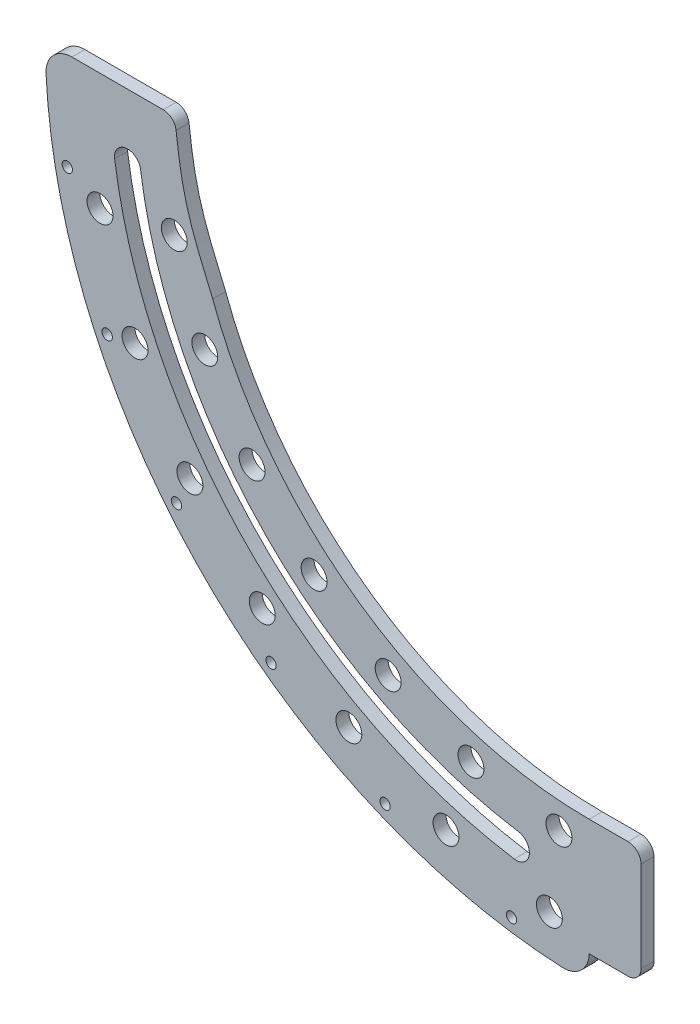
SolidWorks part; units mm, degrees
ref_plane "Front Plane" through (0, 0, 0) normal (0, 0, 1) x (1, 0, 0)
ref_plane "Top Plane" through (0, 0, 0) normal (0, 1, 0) x (1, 0, 0)
ref_plane "Right Plane" through (0, 0, 0) normal (1, 0, 0) x (0, 0, -1)
sketch "Layout" plane through (0, 0, 0) normal (0, 0, 1) x (1, 0, 0)
  line L0 (0, 0) -> (-76.2, 0) construction
  line L1 (-76.2, 0) -> (-203.2, 0) construction
  line L2 (-203.2, 0) -> (-254, 0) construction
  dimension "D1" = 76.2
  dimension "D2" = 127
  dimension "D3" = 50.8
sketch "Sketch1" plane through (0, 0, 0) normal (0, 0, 1) x (1, 0, 0)
  line L0 (0, 0) -> (-203.2, 0) construction
  line L1 (0, 0) -> (0, -203.2) construction
  line L2 (0, -203.2) -> (25.4, -203.2)
  line L3 (0, -254) -> (25.4, -254)
  line L4 (-254, 0) -> (-203.2, 0)
  line L5 (25.4, -203.2) -> (25.4, -254)
  arc A0 (-203.2, 0) -> (0, -203.2) centre (0, 0) ccw
  arc A1 (-254, 0) -> (0, -254) centre (0, 0) ccw
  dimension "D1" = 50.8
  dimension "D2" = 25.4
  dimension "D3" = 203.2
extrude "Boss-Extrude1" add sketch "Sketch1" along normal blind 6.35
ref_plane "Mid_Plane" through (0, 0, 3.175) normal (0, 0, 1) x (1, 0, 0)
sketch "Sketch2" plane through (0, 0, 6.35) normal (0, 0, 1) x (1, 0, 0)
  line L0 (0, 0) -> (-229.3095, 0) construction
  line L1 (0, 0) -> (-226.3753, -31.815) construction
  line L2 (0, 0) -> (-35.7609, -225.7856) construction
  arc A0 (-226.3753, -31.815) -> (-35.7609, -225.7856) centre (0, 0) ccw construction
  arc A1 (-226.3753, -31.815) -> (-35.7609, -225.7856) centre (0, 0) ccw construction
  arc A2 (-232.7264, -32.7076) -> (-36.7642, -232.1201) centre (0, 0) ccw
  arc A3 (-220.0242, -30.9224) -> (-34.7576, -219.451) centre (0, 0) ccw
  arc A4 (-220.0242, -30.9224) -> (-232.7264, -32.7076) centre (-226.3753, -31.815) ccw
  arc A5 (-36.7642, -232.1201) -> (-34.7576, -219.451) centre (-35.7609, -225.7856) ccw
  point P5 (-163.0491, -160.2279)
  dimension "D1" = 73
  dimension "D3" = 12.827
  dimension "D4" = 228.6
  dimension "D2" = 8
extrude "Cut-Extrude1" cut sketch "Sketch2" against normal up to next
fillet "Fillet1" [suppressed] radius 12.7
ref_point "Mid_Point"
sketch "Sketch4" plane through (0, 0, 0) normal (0, 0, -1) x (-1, 0, 0)
  line L0 (254, 0) -> (266.7, 0)
  line L1 (0, -254) -> (0, -266.7)
  arc A0 (0, -254) -> (254, 0) centre (0, 0) ccw construction
  arc A1 (0, -254) -> (254, 0) centre (0, 0) ccw
  arc A2 (0, -266.7) -> (266.7, 0) centre (0, 0) ccw
extrude "Boss-Extrude3" add sketch "Sketch4" against normal up to surface (6.35 mm away) up to face at (-145.6981, -143.1771, 6.35)
fillet "Fillet2" radius 12.7 2 edges at (-266.7, 0, 3.175) (0, -266.7, 3.175)
sketch "Sketch5" plane through (0, 0, 0) normal (0, 0, -1) x (-1, 0, 0)
  line L0 (2.758, -261.6055) -> (3.6103, -266.6756)
  line L1 (0, 0) -> (306.4939, -16.1536) construction
  line L2 (0, -261.62) -> (0.7987, -266.6988)
  line L3 (0, -261.62) -> (-1.3603, -266.6965)
  line L4 (2.758, -261.6055) -> (1.4514, -266.6961)
  line L5 (5.5157, -261.5618) -> (6.4214, -266.6227)
  line L6 (5.5157, -261.5618) -> (4.2628, -266.6659)
  line L7 (8.2728, -261.4892) -> (9.2318, -266.5402)
  line L8 (8.2728, -261.4892) -> (7.0738, -266.6062)
  line L9 (11.029, -261.3874) -> (12.0411, -266.428)
  line L10 (11.029, -261.3874) -> (9.884, -266.5168)
  line L11 (13.7839, -261.2566) -> (14.8492, -266.2863)
  line L12 (13.7839, -261.2566) -> (12.693, -266.3978)
  line L13 (16.5374, -261.0968) -> (17.6555, -266.115)
  line L14 (16.5374, -261.0968) -> (15.5007, -266.2492)
  line L15 (19.2889, -260.908) -> (20.46, -265.914)
  line L16 (19.2889, -260.908) -> (18.3067, -266.071)
  line L17 (22.0384, -260.6901) -> (23.2621, -265.6836)
  line L18 (22.0384, -260.6901) -> (21.1106, -265.8632)
  line L19 (24.7854, -260.4433) -> (26.0617, -265.4236)
  line L20 (24.7854, -260.4433) -> (23.9122, -265.6259)
  line L21 (27.5296, -260.1675) -> (28.8583, -265.1341)
  line L22 (27.5296, -260.1675) -> (26.7111, -265.359)
  line L23 (30.2708, -259.8629) -> (31.6518, -264.8151)
  line L24 (30.2708, -259.8629) -> (29.507, -265.0627)
  line L25 (33.0086, -259.5293) -> (34.4417, -264.4667)
  line L26 (33.0086, -259.5293) -> (32.2997, -264.7369)
  line L27 (35.7427, -259.1669) -> (37.2278, -264.089)
  line L28 (35.7427, -259.1669) -> (35.0888, -264.3817)
  line L29 (38.4729, -258.7757) -> (40.0098, -263.6818)
  line L30 (38.4729, -258.7757) -> (37.874, -263.9971)
  line L31 (41.1988, -258.3557) -> (42.7873, -263.2454)
  line L32 (41.1988, -258.3557) -> (40.6549, -263.5831)
  line L33 (43.9201, -257.9071) -> (45.5601, -262.7797)
  line L34 (43.9201, -257.9071) -> (43.4314, -263.1399)
  line L35 (46.6365, -257.4297) -> (48.3278, -262.2848)
  line L36 (46.6365, -257.4297) -> (46.203, -262.6674)
  line L37 (49.3478, -256.9238) -> (51.0902, -261.7607)
  line L38 (49.3478, -256.9238) -> (48.9695, -262.1657)
  line L39 (52.0535, -256.3893) -> (53.8468, -261.2076)
  line L40 (52.0535, -256.3893) -> (51.7305, -261.6349)
  line L41 (54.7535, -255.8263) -> (56.5975, -260.6254)
  line L42 (54.7535, -255.8263) -> (54.4858, -261.0751)
  line L43 (57.4474, -255.2348) -> (59.3419, -260.0143)
  line L44 (57.4474, -255.2348) -> (57.2351, -260.4862)
  line L45 (60.1349, -254.615) -> (62.0797, -259.3743)
  line L46 (60.1349, -254.615) -> (59.978, -259.8683)
  line L47 (62.8157, -253.9669) -> (64.8106, -258.7054)
  line L48 (62.8157, -253.9669) -> (62.7142, -259.2216)
  line L49 (65.4896, -253.2906) -> (67.5342, -258.0078)
  line L50 (65.4896, -253.2906) -> (65.4434, -258.546)
  line L51 (68.1561, -252.5862) -> (70.2504, -257.2815)
  line L52 (68.1561, -252.5862) -> (68.1654, -257.8418)
  line L53 (70.8151, -251.8536) -> (72.9588, -256.5266)
  line L54 (70.8151, -251.8536) -> (70.8798, -257.1088)
  line L55 (73.4663, -251.0931) -> (75.6591, -255.7432)
  line L56 (73.4663, -251.0931) -> (73.5863, -256.3473)
  line L57 (76.1092, -250.3046) -> (78.3509, -254.9314)
  line L58 (76.1092, -250.3046) -> (76.2846, -255.5573)
  line L59 (78.7437, -249.4884) -> (81.0341, -254.0913)
  line L60 (78.7437, -249.4884) -> (78.9745, -254.7389)
  line L61 (81.3695, -248.6444) -> (83.7082, -253.2229)
  line L62 (81.3695, -248.6444) -> (81.6556, -253.8922)
  line L63 (83.9862, -247.7728) -> (86.373, -252.3263)
  line L64 (83.9862, -247.7728) -> (84.3276, -253.0173)
  line L65 (86.5935, -246.8736) -> (89.0283, -251.4018)
  line L66 (86.5935, -246.8736) -> (86.9902, -252.1142)
  line L67 (89.1913, -245.947) -> (91.6736, -250.4493)
  line L68 (89.1913, -245.947) -> (89.6432, -251.1832)
  line L69 (91.7791, -244.9931) -> (94.3088, -249.4689)
  line L70 (91.7791, -244.9931) -> (92.2862, -250.2242)
  line L71 (94.3567, -244.0119) -> (96.9335, -248.4608)
  line L72 (94.3567, -244.0119) -> (94.919, -249.2374)
  line L73 (96.9239, -243.0037) -> (99.5474, -247.4252)
  line L74 (96.9239, -243.0037) -> (97.5412, -248.2229)
  line L75 (99.4803, -241.9684) -> (102.1502, -246.362)
  line L76 (99.4803, -241.9684) -> (100.1525, -247.1808)
  line L77 (102.0256, -240.9062) -> (104.7417, -245.2714)
  line L78 (102.0256, -240.9062) -> (102.7528, -246.1113)
  line L79 (104.5596, -239.8173) -> (107.3215, -244.1536)
  line L80 (104.5596, -239.8173) -> (105.3416, -245.0144)
  line L81 (107.0819, -238.7017) -> (109.8895, -243.0086)
  line L82 (107.0819, -238.7017) -> (107.9187, -243.8902)
  line L83 (109.5924, -237.5595) -> (112.4452, -241.8367)
  line L84 (109.5924, -237.5595) -> (110.4838, -242.739)
  line L85 (112.0907, -236.391) -> (114.9884, -240.6378)
  line L86 (112.0907, -236.391) -> (113.0366, -241.5608)
  line L87 (114.5765, -235.1962) -> (117.5188, -239.4122)
  line L88 (114.5765, -235.1962) -> (115.5769, -240.3557)
  line L89 (117.0496, -233.9753) -> (120.0362, -238.16)
  line L90 (117.0496, -233.9753) -> (118.1043, -239.124)
  line L91 (119.5096, -232.7283) -> (122.5402, -236.8814)
  line L92 (119.5096, -232.7283) -> (120.6186, -237.8656)
  line L93 (121.9564, -231.4555) -> (125.0306, -235.5764)
  line L94 (121.9564, -231.4555) -> (123.1195, -236.5808)
  line L95 (124.3897, -230.157) -> (127.5071, -234.2452)
  line L96 (124.3897, -230.157) -> (125.6067, -235.2697)
  line L97 (126.8091, -228.8329) -> (129.9695, -232.888)
  line L98 (126.8091, -228.8329) -> (128.0799, -233.9325)
  line L99 (129.2144, -227.4833) -> (132.4174, -231.5049)
  line L100 (129.2144, -227.4833) -> (130.539, -232.5693)
  line L101 (131.6054, -226.1085) -> (134.8505, -230.0961)
  line L102 (131.6054, -226.1085) -> (132.9835, -231.1802)
  line L103 (133.9817, -224.7085) -> (137.2687, -228.6617)
  line L104 (133.9817, -224.7085) -> (135.4132, -229.7654)
  line L105 (136.3432, -223.2836) -> (139.6717, -227.2019)
  line L106 (136.3432, -223.2836) -> (137.8279, -228.3251)
  line L107 (138.6895, -221.8339) -> (142.0591, -225.7169)
  line L108 (138.6895, -221.8339) -> (140.2272, -226.8595)
  line L109 (141.0203, -220.3595) -> (144.4307, -224.2067)
  line L110 (141.0203, -220.3595) -> (142.611, -225.3686)
  line L111 (143.3355, -218.8606) -> (146.7863, -222.6717)
  line L112 (143.3355, -218.8606) -> (144.9789, -223.8526)
  line L113 (145.6348, -217.3374) -> (149.1256, -221.1119)
  line L114 (145.6348, -217.3374) -> (147.3307, -222.3118)
  line L115 (147.9179, -215.79) -> (151.4482, -219.5275)
  line L116 (147.9179, -215.79) -> (149.6662, -220.7463)
  line L117 (150.1846, -214.2186) -> (153.7541, -217.9187)
  line L118 (150.1846, -214.2186) -> (151.985, -219.1562)
  line L119 (152.4345, -212.6235) -> (156.0429, -216.2857)
  line L120 (152.4345, -212.6235) -> (154.2869, -217.5418)
  line L121 (154.6675, -211.0047) -> (158.3143, -214.6287)
  line L122 (154.6675, -211.0047) -> (156.5717, -215.9032)
  line L123 (156.8834, -209.3624) -> (160.5681, -212.9478)
  line L124 (156.8834, -209.3624) -> (158.839, -214.2407)
  line L125 (159.0818, -207.6969) -> (162.8041, -211.2432)
  line L126 (159.0818, -207.6969) -> (161.0887, -212.5543)
  line L127 (161.2625, -206.0083) -> (165.022, -209.5152)
  line L128 (161.2625, -206.0083) -> (163.3205, -210.8442)
  line L129 (163.4253, -204.2969) -> (167.2216, -207.7639)
  line L130 (163.4253, -204.2969) -> (165.5342, -209.1108)
  line L131 (165.5699, -202.5627) -> (169.4025, -205.9895)
  line L132 (165.5699, -202.5627) -> (167.7295, -207.3541)
  line L133 (167.6961, -200.806) -> (171.5647, -204.1922)
  line L134 (167.6961, -200.806) -> (169.9061, -205.5744)
  line L135 (169.8037, -199.0269) -> (173.7077, -202.3722)
  line L136 (169.8037, -199.0269) -> (172.0638, -203.7718)
  line L137 (171.8924, -197.2258) -> (175.8315, -200.5297)
  line L138 (171.8924, -197.2258) -> (174.2024, -201.9465)
  line L139 (173.962, -195.4027) -> (177.9357, -198.665)
  line L140 (173.962, -195.4027) -> (176.3217, -200.0989)
  line L141 (176.0123, -193.558) -> (180.0202, -196.7781)
  line L142 (176.0123, -193.558) -> (178.4213, -198.229)
  line L143 (178.043, -191.6917) -> (182.0846, -194.8694)
  line L144 (178.043, -191.6917) -> (180.5012, -196.337)
  line L145 (180.054, -189.8041) -> (184.1288, -192.939)
  line L146 (180.054, -189.8041) -> (182.5609, -194.4232)
  line L147 (182.0449, -187.8954) -> (186.1526, -190.9872)
  line L148 (182.0449, -187.8954) -> (184.6004, -192.4879)
  line L149 (184.0156, -185.9658) -> (188.1556, -189.0141)
  line L150 (184.0156, -185.9658) -> (186.6194, -190.5311)
  line L151 (185.9658, -184.0156) -> (190.1378, -187.0201)
  line L152 (185.9658, -184.0156) -> (188.6176, -188.5532)
  line L153 (187.8954, -182.0449) -> (192.0988, -185.0053)
  line L154 (187.8954, -182.0449) -> (190.5948, -186.5543)
  line L155 (189.8041, -180.054) -> (194.0384, -182.9699)
  line L156 (189.8041, -180.054) -> (192.5509, -184.5346)
  line L157 (191.6917, -178.043) -> (195.9565, -180.9141)
  line L158 (191.6917, -178.043) -> (194.4856, -182.4945)
  line L159 (193.558, -176.0123) -> (197.8529, -178.8383)
  line L160 (193.558, -176.0123) -> (196.3987, -180.4341)
  line L161 (195.4027, -173.962) -> (199.7272, -176.7426)
  line L162 (195.4027, -173.962) -> (198.2899, -178.3536)
  line L163 (197.2258, -171.8924) -> (201.5793, -174.6272)
  line L164 (197.2258, -171.8924) -> (200.1591, -176.2533)
  line L165 (199.0269, -169.8037) -> (203.4091, -172.4925)
  line L166 (199.0269, -169.8037) -> (202.006, -174.1334)
  line L167 (200.806, -167.6961) -> (205.2162, -170.3385)
  line L168 (200.806, -167.6961) -> (203.8305, -171.9942)
  line L169 (202.5627, -165.5699) -> (207.0005, -168.1656)
  line L170 (202.5627, -165.5699) -> (205.6324, -169.8358)
  line L171 (204.2969, -163.4253) -> (208.7618, -165.9741)
  line L172 (204.2969, -163.4253) -> (207.4114, -167.6586)
  line L173 (206.0083, -161.2625) -> (210.4999, -163.7641)
  line L174 (206.0083, -161.2625) -> (209.1673, -165.4628)
  line L175 (207.6969, -159.0818) -> (212.2146, -161.5359)
  line L176 (207.6969, -159.0818) -> (210.9, -163.2485)
  line L177 (209.3624, -156.8834) -> (213.9058, -159.2897)
  line L178 (209.3624, -156.8834) -> (212.6093, -161.0161)
  line L179 (211.0047, -154.6675) -> (215.5731, -157.0259)
  line L180 (211.0047, -154.6675) -> (214.2949, -158.7658)
  line L181 (212.6235, -152.4345) -> (217.2165, -154.7446)
  line L182 (212.6235, -152.4345) -> (215.9567, -156.4979)
  line L183 (214.2186, -150.1846) -> (218.8358, -152.446)
  line L184 (214.2186, -150.1846) -> (217.5945, -154.2126)
  line L185 (215.79, -147.9179) -> (220.4307, -150.1306)
  line L186 (215.79, -147.9179) -> (219.2081, -151.9101)
  line L187 (217.3374, -145.6348) -> (222.0011, -147.7985)
  line L188 (217.3374, -145.6348) -> (220.7974, -149.5908)
  line L189 (218.8606, -143.3355) -> (223.5469, -145.4499)
  line L190 (218.8606, -143.3355) -> (222.3621, -147.2548)
  line L191 (220.3595, -141.0203) -> (225.0678, -143.0852)
  line L192 (220.3595, -141.0203) -> (223.9021, -144.9024)
  line L193 (221.8339, -138.6895) -> (226.5637, -140.7045)
  line L194 (221.8339, -138.6895) -> (225.4173, -142.534)
  line L195 (223.2836, -136.3432) -> (228.0345, -138.3083)
  line L196 (223.2836, -136.3432) -> (226.9074, -140.1497)
  line L197 (224.7085, -133.9817) -> (229.4798, -135.8966)
  line L198 (224.7085, -133.9817) -> (228.3722, -137.7499)
  line L199 (226.1085, -131.6054) -> (230.8997, -133.4699)
  line L200 (226.1085, -131.6054) -> (229.8117, -135.3347)
  line L201 (227.4833, -129.2144) -> (232.2939, -131.0283)
  line L202 (227.4833, -129.2144) -> (231.2256, -132.9045)
  line L203 (228.8329, -126.8091) -> (233.6623, -128.5722)
  line L204 (228.8329, -126.8091) -> (232.6139, -130.4595)
  line L205 (230.157, -124.3897) -> (235.0048, -126.1017)
  line L206 (230.157, -124.3897) -> (233.9762, -128)
  line L207 (231.4555, -121.9564) -> (236.3211, -123.6173)
  line L208 (231.4555, -121.9564) -> (235.3126, -125.5263)
  line L209 (232.7283, -119.5096) -> (237.6111, -121.1191)
  line L210 (232.7283, -119.5096) -> (236.6229, -123.0387)
  line L211 (233.9753, -117.0496) -> (238.8748, -118.6075)
  line L212 (233.9753, -117.0496) -> (237.9068, -120.5373)
  line L213 (235.1962, -114.5765) -> (240.1119, -116.0827)
  line L214 (235.1962, -114.5765) -> (239.1643, -118.0226)
  line L215 (236.391, -112.0907) -> (241.3223, -113.5449)
  line L216 (236.391, -112.0907) -> (240.3952, -115.4948)
  line L217 (237.5595, -109.5924) -> (242.5059, -110.9946)
  line L218 (237.5595, -109.5924) -> (241.5994, -112.9541)
  line L219 (238.7017, -107.0819) -> (243.6625, -108.4319)
  line L220 (238.7017, -107.0819) -> (242.7767, -110.4009)
  line L221 (239.8173, -104.5596) -> (244.792, -105.8572)
  line L222 (239.8173, -104.5596) -> (243.9271, -107.8353)
  line L223 (240.9062, -102.0256) -> (245.8944, -103.2707)
  line L224 (240.9062, -102.0256) -> (245.0503, -105.2579)
  line L225 (241.9684, -99.4803) -> (246.9694, -100.6727)
  line L226 (241.9684, -99.4803) -> (246.1464, -102.6687)
  line L227 (243.0037, -96.9239) -> (248.017, -98.0636)
  line L228 (243.0037, -96.9239) -> (247.215, -100.0681)
  line L229 (244.0119, -94.3567) -> (249.037, -95.4435)
  line L230 (244.0119, -94.3567) -> (248.2562, -97.4564)
  line L231 (244.9931, -91.7791) -> (250.0293, -92.8128)
  line L232 (244.9931, -91.7791) -> (249.2698, -94.8338)
  line L233 (245.947, -89.1913) -> (250.9939, -90.1718)
  line L234 (245.947, -89.1913) -> (250.2557, -92.2007)
  line L235 (246.8736, -86.5935) -> (251.9305, -87.5208)
  line L236 (246.8736, -86.5935) -> (251.2138, -89.5574)
  line L237 (247.7728, -83.9862) -> (252.8392, -84.8601)
  line L238 (247.7728, -83.9862) -> (252.1439, -86.9041)
  line L239 (248.6444, -81.3695) -> (253.7197, -82.1899)
  line L240 (248.6444, -81.3695) -> (253.0461, -84.2412)
  line L241 (249.4884, -78.7437) -> (254.5721, -79.5107)
  line L242 (249.4884, -78.7437) -> (253.9201, -81.5689)
  line L243 (250.3046, -76.1092) -> (255.3961, -76.8225)
  line L244 (250.3046, -76.1092) -> (254.7659, -78.8875)
  line L245 (251.0931, -73.4663) -> (256.1918, -74.1258)
  line L246 (251.0931, -73.4663) -> (255.5834, -76.1973)
  line L247 (251.8536, -70.8151) -> (256.959, -71.4209)
  line L248 (251.8536, -70.8151) -> (256.3724, -73.4987)
  line L249 (252.5862, -68.1561) -> (257.6977, -68.7081)
  line L250 (252.5862, -68.1561) -> (257.133, -70.7919)
  line L251 (253.2906, -65.4896) -> (258.4077, -65.9876)
  line L252 (253.2906, -65.4896) -> (257.865, -68.0773)
  line L253 (253.9669, -62.8157) -> (259.089, -63.2598)
  line L254 (253.9669, -62.8157) -> (258.5684, -65.3551)
  line L255 (254.615, -60.1349) -> (259.7415, -60.5249)
  line L256 (254.615, -60.1349) -> (259.243, -62.6256)
  line L257 (255.2348, -57.4474) -> (260.3651, -57.7834)
  line L258 (255.2348, -57.4474) -> (259.8888, -59.8892)
  line L259 (255.8263, -54.7535) -> (260.9598, -55.0354)
  line L260 (255.8263, -54.7535) -> (260.5057, -57.1461)
  line L261 (256.3893, -52.0535) -> (261.5254, -52.2813)
  line L262 (256.3893, -52.0535) -> (261.0937, -54.3966)
  line L263 (256.9238, -49.3478) -> (262.0621, -49.5213)
  line L264 (256.9238, -49.3478) -> (261.6526, -51.6412)
  line L265 (257.4297, -46.6365) -> (262.5696, -46.7559)
  line L266 (257.4297, -46.6365) -> (262.1825, -48.8799)
  line L267 (257.9071, -43.9201) -> (263.0479, -43.9853)
  line L268 (257.9071, -43.9201) -> (262.6832, -46.1133)
  line L269 (258.3557, -41.1988) -> (263.497, -41.2098)
  line L270 (258.3557, -41.1988) -> (263.1547, -43.3415)
  line L271 (258.7757, -38.4729) -> (263.9167, -38.4297)
  line L272 (258.7757, -38.4729) -> (263.597, -40.5649)
  line L273 (259.1669, -35.7427) -> (264.3072, -35.6453)
  line L274 (259.1669, -35.7427) -> (264.01, -37.7838)
  line L275 (259.5293, -33.0086) -> (264.6683, -32.857)
  line L276 (259.5293, -33.0086) -> (264.3936, -34.9985)
  line L277 (259.8629, -30.2708) -> (265, -30.065)
  line L278 (259.8629, -30.2708) -> (264.7479, -32.2093)
  line L279 (260.1675, -27.5296) -> (265.3022, -27.2697)
  line L280 (260.1675, -27.5296) -> (265.0727, -29.4165)
  line L281 (260.4433, -24.7854) -> (265.5749, -24.4714)
  line L282 (260.4433, -24.7854) -> (265.3681, -26.6204)
  line L283 (260.6901, -22.0384) -> (265.8181, -21.6703)
  line L284 (260.6901, -22.0384) -> (265.634, -23.8214)
  line L285 (260.908, -19.2889) -> (266.0318, -18.8668)
  line L286 (260.908, -19.2889) -> (265.8704, -21.0198)
  line L287 (261.0968, -16.5374) -> (266.2159, -16.0612)
  line L288 (261.0968, -16.5374) -> (266.0772, -18.2158)
  line L289 (261.2566, -13.7839) -> (266.3705, -13.2539)
  line L290 (261.2566, -13.7839) -> (266.2544, -15.4098)
  line L291 (261.3874, -11.029) -> (266.4954, -10.4451)
  line L292 (261.3874, -11.029) -> (266.4021, -12.602)
  line L301 (0, 0) -> (0, -261.62) construction
  arc A0 (13.3308, -266.3666) -> (266.3664, -13.335) centre (0, 0) ccw construction
  arc A1 (-1.3603, -266.6965) -> (0.7987, -266.6988) centre (0, 0) ccw
  arc A2 (1.4514, -266.6961) -> (3.6103, -266.6756) centre (0, 0) ccw
  arc A3 (4.2628, -266.6659) -> (6.4214, -266.6227) centre (0, 0) ccw
  arc A4 (7.0738, -266.6062) -> (9.2318, -266.5402) centre (0, 0) ccw
  arc A5 (9.884, -266.5168) -> (12.0411, -266.428) centre (0, 0) ccw
  arc A6 (12.693, -266.3978) -> (14.8492, -266.2863) centre (0, 0) ccw
  arc A7 (15.5007, -266.2492) -> (17.6555, -266.115) centre (0, 0) ccw
  arc A8 (18.3067, -266.071) -> (20.46, -265.914) centre (0, 0) ccw
  arc A9 (21.1106, -265.8632) -> (23.2621, -265.6836) centre (0, 0) ccw
  arc A10 (23.9122, -265.6259) -> (26.0617, -265.4236) centre (0, 0) ccw
  arc A11 (26.7111, -265.359) -> (28.8583, -265.1341) centre (0, 0) ccw
  arc A12 (29.507, -265.0627) -> (31.6518, -264.8151) centre (0, 0) ccw
  arc A13 (32.2997, -264.7369) -> (34.4417, -264.4667) centre (0, 0) ccw
  arc A14 (35.0888, -264.3817) -> (37.2278, -264.089) centre (0, 0) ccw
  arc A15 (37.874, -263.9971) -> (40.0098, -263.6818) centre (0, 0) ccw
  arc A16 (40.6549, -263.5831) -> (42.7873, -263.2454) centre (0, 0) ccw
  arc A17 (43.4314, -263.1399) -> (45.5601, -262.7797) centre (0, 0) ccw
  arc A18 (46.203, -262.6674) -> (48.3278, -262.2848) centre (0, 0) ccw
  arc A19 (48.9695, -262.1657) -> (51.0902, -261.7607) centre (0, 0) ccw
  arc A20 (51.7305, -261.6349) -> (53.8468, -261.2076) centre (0, 0) ccw
  arc A21 (54.4858, -261.0751) -> (56.5975, -260.6254) centre (0, 0) ccw
  arc A22 (57.2351, -260.4862) -> (59.3419, -260.0143) centre (0, 0) ccw
  arc A23 (59.978, -259.8683) -> (62.0797, -259.3743) centre (0, 0) ccw
  arc A24 (62.7142, -259.2216) -> (64.8106, -258.7054) centre (0, 0) ccw
  arc A25 (65.4434, -258.546) -> (67.5342, -258.0078) centre (0, 0) ccw
  arc A26 (68.1654, -257.8418) -> (70.2504, -257.2815) centre (0, 0) ccw
  arc A27 (70.8798, -257.1088) -> (72.9588, -256.5266) centre (0, 0) ccw
  arc A28 (73.5863, -256.3473) -> (75.6591, -255.7432) centre (0, 0) ccw
  arc A29 (76.2846, -255.5573) -> (78.3509, -254.9314) centre (0, 0) ccw
  arc A30 (78.9745, -254.7389) -> (81.0341, -254.0913) centre (0, 0) ccw
  arc A31 (81.6556, -253.8922) -> (83.7082, -253.2229) centre (0, 0) ccw
  arc A32 (84.3276, -253.0173) -> (86.373, -252.3263) centre (0, 0) ccw
  arc A33 (86.9902, -252.1142) -> (89.0283, -251.4018) centre (0, 0) ccw
  arc A34 (89.6432, -251.1832) -> (91.6736, -250.4493) centre (0, 0) ccw
  arc A35 (92.2862, -250.2242) -> (94.3088, -249.4689) centre (0, 0) ccw
  arc A36 (94.919, -249.2374) -> (96.9335, -248.4608) centre (0, 0) ccw
  arc A37 (97.5412, -248.2229) -> (99.5474, -247.4252) centre (0, 0) ccw
  arc A38 (100.1525, -247.1808) -> (102.1502, -246.362) centre (0, 0) ccw
  arc A39 (102.7528, -246.1113) -> (104.7417, -245.2714) centre (0, 0) ccw
  arc A40 (105.3416, -245.0144) -> (107.3215, -244.1536) centre (0, 0) ccw
  arc A41 (107.9187, -243.8902) -> (109.8895, -243.0086) centre (0, 0) ccw
  arc A42 (110.4838, -242.739) -> (112.4452, -241.8367) centre (0, 0) ccw
  arc A43 (113.0366, -241.5608) -> (114.9884, -240.6378) centre (0, 0) ccw
  arc A44 (115.5769, -240.3557) -> (117.5188, -239.4122) centre (0, 0) ccw
  arc A45 (118.1043, -239.124) -> (120.0362, -238.16) centre (0, 0) ccw
  arc A46 (120.6186, -237.8656) -> (122.5402, -236.8814) centre (0, 0) ccw
  arc A47 (123.1195, -236.5808) -> (125.0306, -235.5764) centre (0, 0) ccw
  arc A48 (125.6067, -235.2697) -> (127.5071, -234.2452) centre (0, 0) ccw
  arc A49 (128.0799, -233.9325) -> (129.9695, -232.888) centre (0, 0) ccw
  arc A50 (130.539, -232.5693) -> (132.4174, -231.5049) centre (0, 0) ccw
  arc A51 (132.9835, -231.1802) -> (134.8505, -230.0961) centre (0, 0) ccw
  arc A52 (135.4132, -229.7654) -> (137.2687, -228.6617) centre (0, 0) ccw
  arc A53 (137.8279, -228.3251) -> (139.6717, -227.2019) centre (0, 0) ccw
  arc A54 (140.2272, -226.8595) -> (142.0591, -225.7169) centre (0, 0) ccw
  arc A55 (142.611, -225.3686) -> (144.4307, -224.2067) centre (0, 0) ccw
  arc A56 (144.9789, -223.8526) -> (146.7863, -222.6717) centre (0, 0) ccw
  arc A57 (147.3307, -222.3118) -> (149.1256, -221.1119) centre (0, 0) ccw
  arc A58 (149.6662, -220.7463) -> (151.4482, -219.5275) centre (0, 0) ccw
  arc A59 (151.985, -219.1562) -> (153.7541, -217.9187) centre (0, 0) ccw
  arc A60 (154.2869, -217.5418) -> (156.0429, -216.2857) centre (0, 0) ccw
  arc A61 (156.5717, -215.9032) -> (158.3143, -214.6287) centre (0, 0) ccw
  arc A62 (158.839, -214.2407) -> (160.5681, -212.9478) centre (0, 0) ccw
  arc A63 (161.0887, -212.5543) -> (162.8041, -211.2432) centre (0, 0) ccw
  arc A64 (163.3205, -210.8442) -> (165.022, -209.5152) centre (0, 0) ccw
  arc A65 (165.5342, -209.1108) -> (167.2216, -207.7639) centre (0, 0) ccw
  arc A66 (167.7295, -207.3541) -> (169.4025, -205.9895) centre (0, 0) ccw
  arc A67 (169.9061, -205.5744) -> (171.5647, -204.1922) centre (0, 0) ccw
  arc A68 (172.0638, -203.7718) -> (173.7077, -202.3722) centre (0, 0) ccw
  arc A69 (174.2024, -201.9465) -> (175.8315, -200.5297) centre (0, 0) ccw
  arc A70 (176.3217, -200.0989) -> (177.9357, -198.665) centre (0, 0) ccw
  arc A71 (178.4213, -198.229) -> (180.0202, -196.7781) centre (0, 0) ccw
  arc A72 (180.5012, -196.337) -> (182.0846, -194.8694) centre (0, 0) ccw
  arc A73 (182.5609, -194.4232) -> (184.1288, -192.939) centre (0, 0) ccw
  arc A74 (184.6004, -192.4879) -> (186.1526, -190.9872) centre (0, 0) ccw
  arc A75 (186.6194, -190.5311) -> (188.1556, -189.0141) centre (0, 0) ccw
  arc A76 (188.6176, -188.5532) -> (190.1378, -187.0201) centre (0, 0) ccw
  arc A77 (190.5948, -186.5543) -> (192.0988, -185.0053) centre (0, 0) ccw
  arc A78 (192.5509, -184.5346) -> (194.0384, -182.9699) centre (0, 0) ccw
  arc A79 (194.4856, -182.4945) -> (195.9565, -180.9141) centre (0, 0) ccw
  arc A80 (196.3987, -180.4341) -> (197.8529, -178.8383) centre (0, 0) ccw
  arc A81 (198.2899, -178.3536) -> (199.7272, -176.7426) centre (0, 0) ccw
  arc A82 (200.1591, -176.2533) -> (201.5793, -174.6272) centre (0, 0) ccw
  arc A83 (202.006, -174.1334) -> (203.4091, -172.4925) centre (0, 0) ccw
  arc A84 (203.8305, -171.9942) -> (205.2162, -170.3385) centre (0, 0) ccw
  arc A85 (205.6324, -169.8358) -> (207.0005, -168.1656) centre (0, 0) ccw
  arc A86 (207.4114, -167.6586) -> (208.7618, -165.9741) centre (0, 0) ccw
  arc A87 (209.1673, -165.4628) -> (210.4999, -163.7641) centre (0, 0) ccw
  arc A88 (210.9, -163.2485) -> (212.2146, -161.5359) centre (0, 0) ccw
  arc A89 (212.6093, -161.0161) -> (213.9058, -159.2897) centre (0, 0) ccw
  arc A90 (214.2949, -158.7658) -> (215.5731, -157.0259) centre (0, 0) ccw
  arc A91 (215.9567, -156.4979) -> (217.2165, -154.7446) centre (0, 0) ccw
  arc A92 (217.5945, -154.2126) -> (218.8358, -152.446) centre (0, 0) ccw
  arc A93 (219.2081, -151.9101) -> (220.4307, -150.1306) centre (0, 0) ccw
  arc A94 (220.7974, -149.5908) -> (222.0011, -147.7985) centre (0, 0) ccw
  arc A95 (222.3621, -147.2548) -> (223.5469, -145.4499) centre (0, 0) ccw
  arc A96 (223.9021, -144.9024) -> (225.0678, -143.0852) centre (0, 0) ccw
  arc A97 (225.4173, -142.534) -> (226.5637, -140.7045) centre (0, 0) ccw
  arc A98 (226.9074, -140.1497) -> (228.0345, -138.3083) centre (0, 0) ccw
  arc A99 (228.3722, -137.7499) -> (229.4798, -135.8966) centre (0, 0) ccw
  arc A100 (229.8117, -135.3347) -> (230.8997, -133.4699) centre (0, 0) ccw
  arc A101 (231.2256, -132.9045) -> (232.2939, -131.0283) centre (0, 0) ccw
  arc A102 (232.6139, -130.4595) -> (233.6623, -128.5722) centre (0, 0) ccw
  arc A103 (233.9762, -128) -> (235.0048, -126.1017) centre (0, 0) ccw
  arc A104 (235.3126, -125.5263) -> (236.3211, -123.6173) centre (0, 0) ccw
  arc A105 (236.6229, -123.0387) -> (237.6111, -121.1191) centre (0, 0) ccw
  arc A106 (237.9068, -120.5373) -> (238.8748, -118.6075) centre (0, 0) ccw
  arc A107 (239.1643, -118.0226) -> (240.1119, -116.0827) centre (0, 0) ccw
  arc A108 (240.3952, -115.4948) -> (241.3223, -113.5449) centre (0, 0) ccw
  arc A109 (241.5994, -112.9541) -> (242.5059, -110.9946) centre (0, 0) ccw
  arc A110 (242.7767, -110.4009) -> (243.6625, -108.4319) centre (0, 0) ccw
  arc A111 (243.9271, -107.8353) -> (244.792, -105.8572) centre (0, 0) ccw
  arc A112 (245.0503, -105.2579) -> (245.8944, -103.2707) centre (0, 0) ccw
  arc A113 (246.1464, -102.6687) -> (246.9694, -100.6727) centre (0, 0) ccw
  arc A114 (247.215, -100.0681) -> (248.017, -98.0636) centre (0, 0) ccw
  arc A115 (248.2562, -97.4564) -> (249.037, -95.4435) centre (0, 0) ccw
  arc A116 (249.2698, -94.8338) -> (250.0293, -92.8128) centre (0, 0) ccw
  arc A117 (250.2557, -92.2007) -> (250.9939, -90.1718) centre (0, 0) ccw
  arc A118 (251.2138, -89.5574) -> (251.9305, -87.5208) centre (0, 0) ccw
  arc A119 (252.1439, -86.9041) -> (252.8392, -84.8601) centre (0, 0) ccw
  arc A120 (253.0461, -84.2412) -> (253.7197, -82.1899) centre (0, 0) ccw
  arc A121 (253.9201, -81.5689) -> (254.5721, -79.5107) centre (0, 0) ccw
  arc A122 (254.7659, -78.8875) -> (255.3961, -76.8225) centre (0, 0) ccw
  arc A123 (255.5834, -76.1973) -> (256.1918, -74.1258) centre (0, 0) ccw
  arc A124 (256.3724, -73.4987) -> (256.959, -71.4209) centre (0, 0) ccw
  arc A125 (257.133, -70.7919) -> (257.6977, -68.7081) centre (0, 0) ccw
  arc A126 (257.865, -68.0773) -> (258.4077, -65.9876) centre (0, 0) ccw
  arc A127 (258.5684, -65.3551) -> (259.089, -63.2598) centre (0, 0) ccw
  arc A128 (259.243, -62.6256) -> (259.7415, -60.5249) centre (0, 0) ccw
  arc A129 (259.8888, -59.8892) -> (260.3651, -57.7834) centre (0, 0) ccw
  arc A130 (260.5057, -57.1461) -> (260.9598, -55.0354) centre (0, 0) ccw
  arc A131 (261.0937, -54.3966) -> (261.5254, -52.2813) centre (0, 0) ccw
  arc A132 (261.6526, -51.6412) -> (262.0621, -49.5213) centre (0, 0) ccw
  arc A133 (262.1825, -48.8799) -> (262.5696, -46.7559) centre (0, 0) ccw
  arc A134 (262.6832, -46.1133) -> (263.0479, -43.9853) centre (0, 0) ccw
  arc A135 (263.1547, -43.3415) -> (263.497, -41.2098) centre (0, 0) ccw
  arc A136 (263.597, -40.5649) -> (263.9167, -38.4297) centre (0, 0) ccw
  arc A137 (264.01, -37.7838) -> (264.3072, -35.6453) centre (0, 0) ccw
  arc A138 (264.3936, -34.9985) -> (264.6683, -32.857) centre (0, 0) ccw
  arc A139 (264.7479, -32.2093) -> (265, -30.065) centre (0, 0) ccw
  arc A140 (265.0727, -29.4165) -> (265.3022, -27.2697) centre (0, 0) ccw
  arc A141 (265.3681, -26.6204) -> (265.5749, -24.4714) centre (0, 0) ccw
  arc A142 (265.634, -23.8214) -> (265.8181, -21.6703) centre (0, 0) ccw
  arc A143 (265.8704, -21.0198) -> (266.0318, -18.8668) centre (0, 0) ccw
  arc A144 (266.0772, -18.2158) -> (266.2159, -16.0612) centre (0, 0) ccw
  arc A145 (266.2544, -15.4098) -> (266.3705, -13.2539) centre (0, 0) ccw
  arc A146 (266.4021, -12.602) -> (266.4954, -10.4451) centre (0, 0) ccw
  dimension "D1" = 2.159
  dimension "D2" = 146
  dimension "D4" = 261.62
extrude "Cut-Extrude2" [suppressed] cut sketch "Sketch5" against normal up to surface (6.35 mm away) up to face at (-145.6981, -143.1771, 6.35)
sketch "Sketch6" plane through (0, 0, 6.35) normal (0, 0, 1) x (1, 0, 0)
  line L0 (0, 0) -> (-202.3753, -163.7976) construction
  circle A1 centre (-255.9253, -47.8297) radius 2.54
  circle A2 centre (-236.3726, -109.1487) radius 2.54
  circle A3 centre (-202.3753, -163.7976) radius 2.54
  circle A4 centre (-156.0111, -208.437) radius 2.54
  circle A5 centre (-100.1131, -240.3389) radius 2.54
  circle A6 centre (-38.0972, -257.5539) radius 2.54
  point P15 (0, 0)
  dimension "D1" = 6
extrude "Cut-Extrude3" cut sketch "Sketch6" against normal through all
sketch "Sketch9" plane through (0, 0, 6.35) normal (0, 0, 1) x (1, 0, 0)
  line L0 (25.4, -203.2) -> (0, -203.2) construction
  line L1 (25.4, -203.2) -> (0, -203.2)
  line L2 (25.4, -196.85) -> (0, -196.85)
  line L3 (25.4, -203.2) -> (25.4, -196.85)
  arc A1 (-203.2, 0) -> (0, -203.2) centre (0, 0) ccw construction
  arc A2 (-203.2, 0) -> (0, -203.2) centre (0, 0) ccw
  arc A3 (-184.643, -68.2412) -> (0, -196.85) centre (0, 0) ccw
  arc A4 (-196.85, 0) -> (0, -196.85) centre (0, 0) ccw construction
  spline S0 degree 3 poles (-203.2, 0) (-199.8847, -32.721) (-195.8268, -42.2466) (-184.643, -68.2412) knots 0 0 0 0 1 1 1 1
  dimension "D1" = 6.35
extrude "Boss-Extrude4" add sketch "Sketch9" against normal up to surface (6.35 mm away) up to face at (-233.8326, -109.1487, 0)
sketch "Sketch10" plane through (0, 0, 0) normal (0, 0, -1) x (-1, 0, 0)
  line L0 (0, 0) -> (14.8412, -209.1023) construction
  line L1 (0, 0) -> (57.9917, -201.4472) construction
  line L2 (0, 0) -> (19.5425, -245.8839) construction
  line L3 (0, 0) -> (70.2376, -236.4476) construction
  circle A0 centre (0, 0) radius 209.6283 construction
  circle A1 centre (14.8412, -209.1023) radius 6.35
  circle A2 centre (57.9917, -201.4472) radius 6.35
  circle A3 centre (98.6077, -184.988) radius 6.35
  circle A4 centre (134.914, -160.4439) radius 6.35
  circle A5 centre (165.324, -128.8876) radius 6.35
  circle A6 centre (188.5085, -91.6983) radius 6.35
  circle A7 centre (203.4542, -50.5013) radius 6.35
  circle A8 centre (0, 0) radius 246.6593 construction
  circle A9 centre (19.5425, -245.8839) radius 6.35
  circle A10 centre (70.2376, -236.4476) radius 6.35
  circle A11 centre (117.8629, -216.6775) radius 6.35
  circle A12 centre (160.3371, -187.4375) radius 6.35
  circle A13 centre (195.8038, -150.0055) radius 6.35
  circle A14 centre (222.7129, -106.0177) radius 6.35
  circle A15 centre (239.8884, -57.3963) radius 6.35
  dimension "D1" = 7
  dimension "D3" = 12.7
  dimension "D2" = 12
  dimension "D5" = 12
  dimension "D4" = 7
extrude "Cut-Extrude4" cut sketch "Sketch10" against normal through all
fillet "Fillet4" radius 6.35 3 edges at (25.4, -196.85, 3.175) (25.4, -254, 3.175) (-203.2, 0, 3.175)
